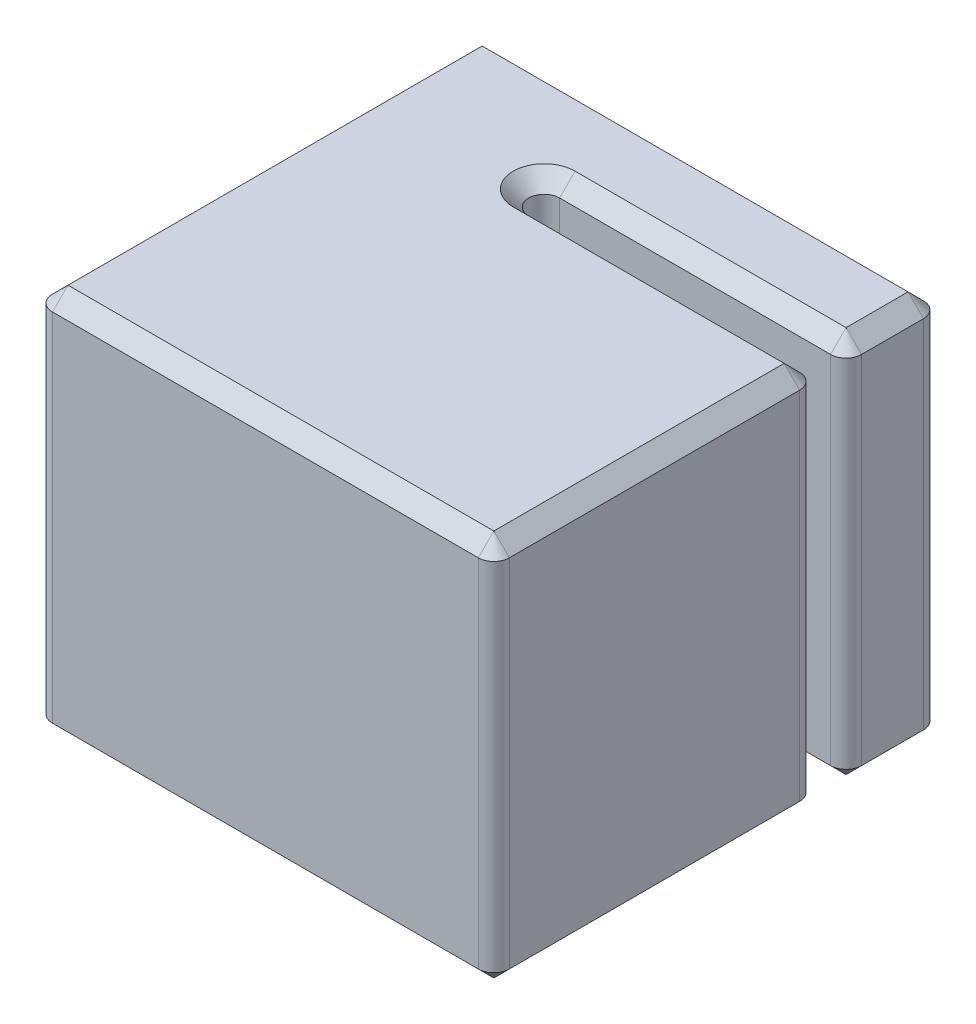
SolidWorks part; units mm, degrees
ref_plane "Front Plane" through (0, 0, 0) normal (0, 0, 1) x (1, 0, 0)
ref_plane "Top Plane" through (0, 0, 0) normal (0, 1, 0) x (1, 0, 0)
ref_plane "Right Plane" through (0, 0, 0) normal (1, 0, 0) x (0, 0, -1)
sketch "Sketch1" plane through (0, 0, 0) normal (0, 1, 0) x (1, 0, 0)
  line L0 (0, 0.4) -> (7, 0.4)
  line L1 (-0.4, 0) -> (4.8195, 0) construction
  line L2 (7.4, 0.8) -> (7.4, 2.4)
  line L3 (7, 2.8) -> (-4, 2.8)
  line L7 (0, -0.4) -> (7, -0.4)
  line L8 (-4.4, 2.4) -> (-4.4, -8.3)
  line L9 (-4, -8.7) -> (7, -8.7)
  line L10 (7.4, -8.3) -> (7.4, -0.8)
  arc A0 (0, 0.4) -> (0, -0.4) centre (0, 0) ccw
  arc A1 (7, 0.4) -> (7.4, 0.8) centre (7, 0.8) ccw
  arc A2 (7.4, 2.4) -> (7, 2.8) centre (7, 2.4) ccw
  arc A3 (-4, 2.8) -> (-4.4, 2.4) centre (-4, 2.4) ccw
  arc A6 (7, -0.4) -> (7.4, -0.8) centre (7, -0.8) cw
  arc A7 (-4.4, -8.3) -> (-4, -8.7) centre (-4, -8.3) ccw
  arc A8 (7, -8.7) -> (7.4, -8.3) centre (7, -8.3) ccw
  dimension "D1" = 0.8
  dimension "D2" = 2.4
  dimension "D3" = 7
  dimension "D4" = 8.3
  dimension "D5" = 4
extrude "Boss-Extrude1" add sketch "Sketch1" along normal blind 10
chamfer "Chamfer1" distance 0.4 angle 45 28 edges at (3.5, 0, -0.4) (7.2828, 0, -0.5172) (7.4, 0, -1.6) (7.2828, 0, -2.6828) (1.5, 0, -2.8) (-4.2828, 0, -2.6828) (7.2828, 0, 0.5172) (3.5, 0, 0.4) (-0.4, 0, 0) (3.5, 10, 0.4) (7.2828, 10, 0.5172) (-4.2828, 10, -2.6828) (1.5, 10, -2.8) (7.2828, 10, -2.6828) (7.4, 10, -1.6) (7.2828, 10, -0.5172) (3.5, 10, -0.4) (-0.4, 10, 0) (-4.4, 0, 2.95) (-4.2828, 0, 8.5828) (1.5, 0, 8.7) (7.2828, 0, 8.5828) (7.4, 0, 4.55) (7.4, 10, 4.55) (7.2828, 10, 8.5828) (1.5, 10, 8.7) (-4.2828, 10, 8.5828) (-4.4, 10, 2.95)
